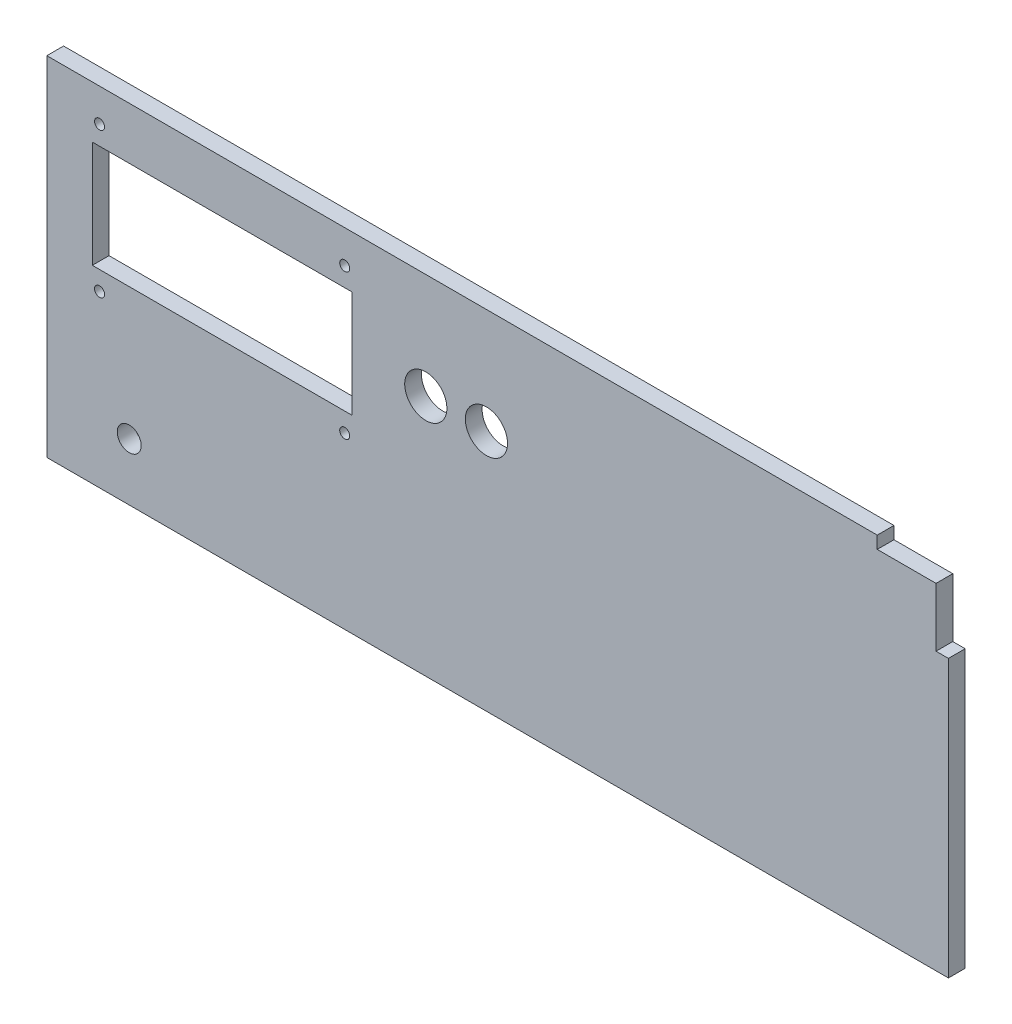
SolidWorks part; units mm, degrees
ref_plane "Front Plane" through (0, 0, 0) normal (0, 0, 1) x (1, 0, 0)
ref_plane "Top Plane" through (0, 0, 0) normal (0, 1, 0) x (1, 0, 0)
ref_plane "Right Plane" through (0, 0, 0) normal (1, 0, 0) x (0, 0, -1)
sketch "Sketch1" plane through (0, 0, 0) normal (0, 0, 1) x (1, 0, 0)
  line L0 (66.5, 92) -> (66.5, 112.25) construction
  line L1 (0, 0) -> (342, 0)
  line L2 (0, 0) -> (0, 132)
  line L13 (20, 64.5) -> (113, 119.5) construction
  line L14 (20, 119.5) -> (113, 64.5) construction
  line L15 (115.75, 92) -> (143.75, 92) construction
  line L16 (143.75, 92) -> (166.75, 92) construction
  line L17 (17.25, 71.75) -> (17.25, 21.75) construction
  line L18 (17.25, 21.75) -> (31.25, 21.75) construction
  line L19 (17.25, 71.75) -> (115.75, 71.75)
  line L20 (17.25, 71.75) -> (17.25, 112.25)
  line L21 (17.25, 112.25) -> (115.75, 112.25)
  line L22 (115.75, 71.75) -> (115.75, 112.25)
  line L23 (17.25, 71.75) -> (115.75, 112.25) construction
  line L24 (17.25, 112.25) -> (115.75, 71.75) construction
  line L25 (315, 132) -> (315, 127.3)
  line L26 (315, 127.3) -> (337.3, 127.3)
  line L27 (337.3, 127.3) -> (337.3, 105)
  line L28 (337.3, 105) -> (342, 105)
  line L29 (342, 0) -> (342, 105)
  line L30 (0, 132) -> (315, 132)
  circle A0 centre (113, 119.5) radius 1.9
  circle A1 centre (113, 64.5) radius 1.9
  circle A2 centre (20, 64.5) radius 1.9
  circle A3 centre (20, 119.5) radius 1.9
  circle A4 centre (143.75, 92) radius 8
  circle A5 centre (166.75, 92) radius 8
  circle A6 centre (31.25, 21.75) radius 4.55
  point P1 (339.65, 105)
  point P5 (66.5, 92)
  point P22 (66.5, 92)
  dimension "D5" = 3.8
  dimension "D6" = 3.8
  dimension "D7" = 3.8
  dimension "D8" = 3.8
  dimension "D16" = 28
  dimension "D17" = 16
  dimension "D19" = 16
  dimension "D22" = 9.1
  dimension "D1" = 132
  dimension "D3" = 55
  dimension "D4" = 93
  dimension "D9" = 66.5
  dimension "D10" = 4.7
  dimension "D11" = 98.5
  dimension "D12" = 40.5
  dimension "D13" = 61.2
  dimension "D14" = 17.25
  dimension "D15" = 59.4
  dimension "D18" = 23
  dimension "D20" = 50
  dimension "D21" = 14
  dimension "D23" = 4.7
  dimension "D24" = 27
  dimension "D25" = 27
  dimension "D26" = 342
  dimension "D27" = 19.75
extrude "Boss-Extrude1" add sketch "Sketch1" along normal blind 6.35
